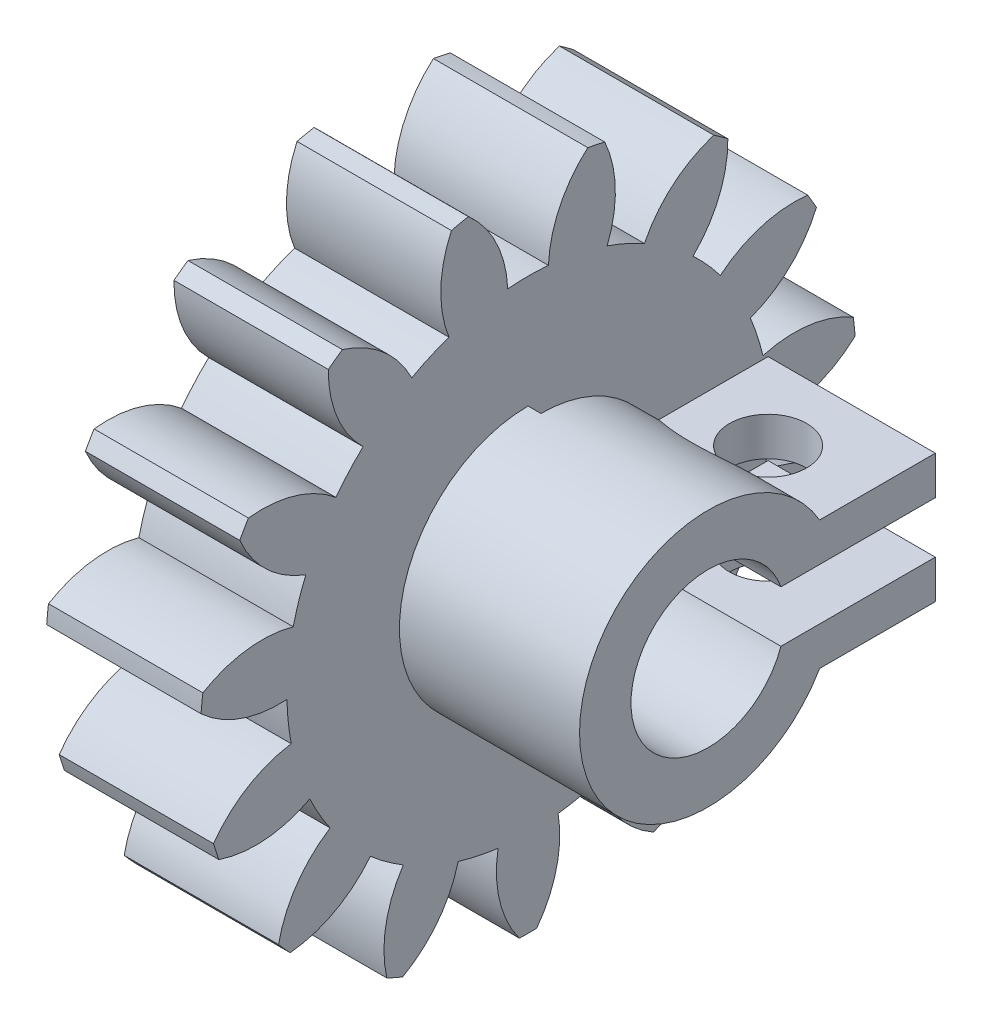
SolidWorks part; units mm, degrees
ref_plane "Plane1" through (0, 0, 0) normal (0, 0, 1) x (1, 0, 0)
ref_plane "Plane2" through (0, 0, 0) normal (0, 1, 0) x (1, 0, 0)
ref_plane "Plane3" through (0, 0, 0) normal (1, 0, 0) x (0, 0, -1)
sketch "HoldingSke" plane through (0, 0, 0) normal (0, 1, 0) x (1, 0, 0)
  line L0 (0, 0) -> (0.644, -0.1725)
  line L1 (-15, 0) -> (100, 0) construction
  line L2 (0, 0) -> (-2.1039, 2.3779)
  line L3 (0, 0) -> (-11.863, 4.5341)
  line L4 (0, 0) -> (8.3417, 2.2352)
  line L5 (0, 0) -> (-46.8476, -17.4728)
  line L6 (0, 0) -> (-4.9738, -3.3558)
  line L7 (-2.1039, 2.3779) -> (8.6586, 51.2059)
  line L8 (-76.2, 54.61) -> (-75.2, 54.61)
  line L9 (-71.009, 38.7566) -> (-53.1078, 45.2721)
  line L10 (-76.2, 71.12) -> (104.1128, 71.12)
  line L11 (0, 0) -> (-6, 0)
  line L12 (-76.2, 101.6) -> (-76.147, 101.6)
  line L13 (24.9733, 27.94) -> (52.9518, 28.4284)
  line L14 (24.9733, 27.94) -> (24.9743, 27.94)
  line L15 (24.9733, 27.94) -> (100.4006, 29.5858)
  line L16 (-63.627, -1.5) -> (-12.827, -1.5)
  circle A0 centre (0, 0) radius 3
  circle A1 centre (0, 0) radius 9.374
  circle A2 centre (0, 0) radius 37.5
  circle A3 centre (0, 0) radius 3
  dimension "Num_teeth" = 15
  dimension "Pitch_radius" = 180.3128
  dimension "Width" = 6
  dimension "Thickness" = 6
sketch "BasProSke" plane through (0, 0, 0) normal (0, 1, 0) x (1, 0, 0)
  line L0 (-10, 0) -> (60, 0) construction
  line L1 (0, 0) -> (0, 12.75)
  line L2 (0, 0) -> (6, 0)
  line L3 (6, 0) -> (6, 12.75)
  line L4 (6, 12.75) -> (0, 12.75)
  dimension "Thickness" = 6
  dimension "Diameter" = 25.5
revolve "Base-Revolve" add sketch "BasProSke" angle 360 about L0
sketch "TooCutSke" plane through (0, 0, 0) normal (1, 0, 0) x (0, 0, -1)
  line L1 (0, 0) -> (0, 107) construction
  line L2 (0, 0) -> (-1.2686, 11.1782) construction
  line L3 (0, 0) -> (-4.6563, 21.9061) construction
  line L4 (-1.2686, 11.1782) -> (-2.3281, 10.953) construction
  arc A0 (0.7915, 9.3405) -> (-0.7915, 9.3405) centre (0, 0) ccw
  arc A1 (2.3447, 12.5584) -> (-2.3447, 12.5584) centre (0, 0) ccw
  circle A2 centre (0, 0) radius 11.25 construction
  circle A3 centre (0, 0) radius 10.5715 construction
  arc A4 (-0.7915, 9.3405) -> (-2.3447, 12.5584) centre (-5.2877, 9.1541) ccw
  arc A5 (2.3447, 12.5584) -> (0.7915, 9.3405) centre (5.2877, 9.1541) ccw
extrude "ToothCut" cut sketch "TooCutSke" along normal through all
fillet "Breaks" [suppressed] radius 0.03 tangent propagation no
fillet "RootFillets" [suppressed] radius 0.376
pattern_circular "TeethCuts" count 15 every 24 about axis through (-10, 0, 0) along (1, 0, 0) of "ToothCut", "RootFillets", "Breaks"
sketch "HubNeaOneSke" plane through (0, 0, 0) normal (-1, 0, 0) x (0, 0, 1)
  circle A0 centre (0, 0) radius 9.374
  dimension "Diameter" = 18.748
extrude "HubNearOne" [suppressed] add sketch "HubNeaOneSke" along normal blind 44.0001
sketch "HubNeaBotSke" plane through (0, 0, 0) normal (-1, 0, 0) x (0, 0, 1)
  circle A0 centre (0, 0) radius 9.374
  dimension "Diameter" = 18.748
extrude "HubNearBoth" [suppressed] add sketch "HubNeaBotSke" along normal blind 22
ref_plane "FarPln" through (6, 0, 0) normal (1, 0, 0) x (0, 0, -1)
sketch "HubFarSke" plane through (6, 0, 0) normal (1, 0, 0) x (0, 0, -1)
  circle A0 centre (0, 0) radius 9.374
  dimension "Diameter" = 18.748
extrude "HubFar" [suppressed] add sketch "HubFarSke" along normal blind 22
sketch "BorSke" plane through (0, 0, 0) normal (1, 0, 0) x (0, 0, -1)
  circle A0 centre (0, 0) radius 3
  dimension "Diameter" = 6
extrude "Bore" cut sketch "BorSke" along normal mid plane 100.0001
sketch "KeySke" plane through (0, 0, 0) normal (1, 0, 0) x (0, 0, -1)
  line L0 (-1, 0) -> (-1, 4)
  line L1 (-1, 4) -> (1, 4)
  line L2 (1, 4) -> (1, 0)
  line L3 (0, 0) -> (0, 34) construction
  line L4 (-1, 0) -> (1, 0)
  dimension "Width" = 2
extrude "Keyway" [suppressed] cut sketch "KeySke" along normal mid plane 100.0001
pattern_circular "Keyway2" [suppressed] count 2 every 90 about axis through (-10, 0, 0) along (1, 0, 0) reverse direction yes
sketch "Sketch1" plane through (6, 0, 0) normal (1, 0, 0) x (0, 0, -1)
  circle A0 centre (0, 0) radius 5
  circle A1 centre (0, 0) radius 3 construction
  circle A2 centre (0, 0) radius 3
  dimension "D1" = 2
extrude "Boss-Extrude1" add sketch "Sketch1" along normal blind 7
sketch "Sketch2" plane through (13, 0, 0) normal (1, 0, 0) x (0, 0, -1)
  line L1 (1.3232, -1) -> (5.7963, -1)
  line L2 (1.3232, -1) -> (1.3232, 1)
  line L3 (1.3232, 1) -> (5.7963, 1)
  line L4 (5.7963, -1) -> (5.7963, 1)
  line L5 (1.3232, -1) -> (5.7963, 1) construction
  line L6 (1.3232, 1) -> (5.7963, -1) construction
  point P0 (3.5597, 0)
  point P5 (3.5998, 0)
  point P6 (3.5597, 0)
  point P8 (3.5597, 0)
  dimension "D1" = 2
extrude "Cut-Extrude1" cut sketch "Sketch2" against normal up to surface (7 mm away) contours L3 L4 L1 L2 up to face at (6, 0, 0)
sketch "Sketch3" plane through (0, -1, 0) normal (0, 1, 0) x (1, 0, 0)
  line L1 (6, 2.8284) -> (13, 2.8284)
  line L2 (6, 2.8284) -> (6, 8.8284)
  line L3 (6, 8.8284) -> (13, 8.8284)
  line L4 (13, 2.8284) -> (13, 8.8284)
  dimension "D1" = 6
extrude "Boss-Extrude2" add sketch "Sketch3" against normal blind 1.5
mirror "Mirror2" about plane through (0, 0, 0) normal (0, 1, 0) of "Boss-Extrude2"
sketch "Sketch4" plane through (0, -1, 0) normal (0, 1, 0) x (1, 0, 0)
  line L0 (6, 2.8284) -> (13, 8.8284) construction
  line L1 (6, 8.8284) -> (13, 2.8284) construction
  circle A0 centre (9.5, 5.8284) radius 1.5
  dimension "D1" = 3
extrude "Cut-Extrude2" cut sketch "Sketch4" against normal through all and the other way through all contours A0
sketch "Sketch5" plane through (0, 2.5, 0) normal (0, 1, 0) x (1, 0, 0)
  line L0 (6, 8.8284) -> (13, 2.8284) construction
  circle A0 centre (9.5, 5.8284) radius 3
  dimension "D1" = 6
extrude "Cut-Extrude3" cut sketch "Sketch5" along normal through all contours A0
mirror "Mirror3" about plane through (0, 0, 0) normal (0, 1, 0) of "Cut-Extrude3"
sketch "Sketch6" plane through (0, 0, 0) normal (0, 0, 1) x (1, 0, 0)
  line L0 (6, -8.278) -> (6, -5.3558) construction
  line L1 (6.5, 13.3231) -> (6, 13.3231)
  line L2 (6.5, 13.3231) -> (6.5, -14.0698)
  line L3 (6.5, -14.0698) -> (6, -14.0698)
  line L4 (6, 13.3231) -> (6, -14.0698)
  line L5 (6.5, 13.3231) -> (6, -14.0698) construction
  line L6 (6.5, -14.0698) -> (6, 13.3231) construction
  point P0 (6.25, -0.3734)
  point P7 (7.1755, 0)
  dimension "D1" = 0.5
extrude "Cut-Extrude4" cut sketch "Sketch6" against normal through all
equation "' \"Module@HoldingSke\" = 6.35"
equation "' \"Num_teeth@HoldingSke\" = 12"
equation "' \"Ap@HoldingSke\" =  20"
equation "' \"Ap@HoldingSke\" = 20"
equation "' \"Width@HoldingSke\" = 0.5 * 25.4"
equation "' \"Hub_dia@HoldingSke\"= 1 * 25.4"
equation "' \"Hub_dia@HoldingSke\" = 1 * 25.4"
equation "' \"Overall_len@HoldingSke\" = 1.0 * 25.4"
equation "' \"Bore@HoldingSke\" = 0.75 * 25.4"
equation "' \"T_dim@HoldingSke\" = 0.1 * 25.4"
equation "' \"Width@KeySke\" = 0.25 * 25.4"
equation "' \"Show_teeth@HoldingSke\" = 13"
equation "' \"Backlash@HoldingSke\" = 0.009 * 25.4"
equation "' \"Addendum_fac@HoldingSke\" = 1.0"
equation "' \"Dedendum_fac@HoldingSke\" = 1.25"
equation "' \"Dedendum_add@HoldingSke\" = 0.00005 * 25.4"
equation "' \"Clearance_fac@HoldingSke\" = 0.25"
equation "\"Pitch@HoldingSke\" = 1 / \"Module@HoldingSke\""
equation "\"Overcut_dia@TooCutSke\" = (\"Num_teeth@HoldingSke\" + 2 * \"Addendum_fac@HoldingSke\") / \"Pitch@HoldingSke\" + 0.002 * 25.4"
equation "\"Pitch_dia@TooCutSke\" = \"Num_teeth@HoldingSke\" / \"Pitch@HoldingSke\""
equation "\"Base_dia@TooCutSke\" = \"Num_teeth@HoldingSke\" / \"Pitch@HoldingSke\" * cos((\"Ap@HoldingSke\"  * 3.14159265 / 180))"
equation "\"Root_dia@TooCutSke\" = (\"Num_teeth@HoldingSke\" + 2) / \"Pitch@HoldingSke\" - 2 * (\"Addendum_fac@HoldingSke\" + \"Dedendum_fac@HoldingSke\") / \"Pitch@HoldingSke\" - \"Dedendum_add@HoldingSke\" * 2"
equation "\"Half_ang@TooCutSke\" = 180 / \"Num_teeth@HoldingSke\""
equation "\"Half_CT@TooCutSke\" = \"Num_teeth@HoldingSke\" / \"Pitch@HoldingSke\" * sin((3.14159265 / 2 / \"Num_teeth@HoldingSke\")) / 2 - 7 * \"Backlash@HoldingSke\" / 4"
equation "\"Flank_rad@TooCutSke\" = \"Num_teeth@HoldingSke\" / \"Pitch@HoldingSke\" / 5"
equation "\"Radius@RootFillets\" = \"Clearance_fac@HoldingSke\" / \"Pitch@HoldingSke\" + \"Dedendum_add@HoldingSke\""
equation "\"Break_rad@Breaks\" = 0.02 / \"Pitch@HoldingSke\""
equation "\"Thickness@HoldingSke\" = \"Width@HoldingSke\""
equation "\"OAL@HoldingSke\" = \"Thickness@HoldingSke\""
equation "\"MHD@HoldingSke\" = (\"Num_teeth@HoldingSke\" + 2) / \"Pitch@HoldingSke\" - 2 * (\"Addendum_fac@HoldingSke\" + \"Dedendum_fac@HoldingSke\")  / \"Pitch@HoldingSke\" - \"Dedendum_add@HoldingSke\" * 2"
equation "\"MBD@HoldingSke\" = (\"Num_teeth@HoldingSke\" + 2) / \"Pitch@HoldingSke\" - 2 * (\"Addendum_fac@HoldingSke\" + \"Dedendum_fac@HoldingSke\")  / \"Pitch@HoldingSke\" - \"Dedendum_add@HoldingSke\" * 2 - 0.002 * 25.4"
equation "\"MHD@HoldingSke\" = ((sgn( \"MHD@HoldingSke\" - \"Hub_dia@HoldingSke\" )-1)*( \"MHD@HoldingSke\" - \"Hub_dia@HoldingSke\" ))/-2+ \"Hub_dia@HoldingSke\""
equation "\"MBD@HoldingSke\" = ((sgn( \"MBD@HoldingSke\" - \"Bore@HoldingSke\" )-1)*( \"MBD@HoldingSke\" - \"Bore@HoldingSke\" ))/-2+ \"Bore@HoldingSke\""
equation "\"OAL@HoldingSke\" = ((sgn( \"OAL@HoldingSke\" - \"Overall_len@HoldingSke\" )+1)*( \"OAL@HoldingSke\" - \"Overall_len@HoldingSke\" ))/2 + \"Overall_len@HoldingSke\" + 0.000002 * 25.4"
equation "\"Num_teeth@TeethCuts\" = int( \"Show_teeth@HoldingSke\" ) + 1"
equation "\"Num_teeth@TeethCuts\" = ((sgn( \"Num_teeth@TeethCuts\" - \"Num_teeth@HoldingSke\" )-1)*( \"Num_teeth@TeethCuts\" - \"Num_teeth@HoldingSke\" ))/-2+ \"Num_teeth@HoldingSke\""
equation "\"Num_teeth@TeethCuts\" = ((sgn( \"Num_teeth@TeethCuts\" - 2.0)+1)*( \"Num_teeth@TeethCuts\" - 2.0))/2 +2.0"
equation "\"Angle@TeethCuts\" = 360.0 / \"Num_teeth@HoldingSke\""
equation "\"Diameter@BasProSke\" = (\"Num_teeth@HoldingSke\" + 2 * \"Addendum_fac@HoldingSke\") / \"Pitch@HoldingSke\""
equation "\"Thickness@BasProSke\"  = \"Thickness@HoldingSke\""
equation "' \"Fillet_rad@BasProSke\" =  \"Thickness@HoldingSke\" * 0.05"
equation "' \"Fillet_rad@BasProSke\" = \"Thickness@HoldingSke\" * 0.05"
equation "\"MHD@HoldingSke\" = ((sgn( \"MHD@HoldingSke\" - \"Root_dia@TooCutSke\" )-1)*( \"MHD@HoldingSke\" - \"Root_dia@TooCutSke\" ))/-2+ \"Root_dia@TooCutSke\""
equation "\"Diameter@HubNeaOneSke\" = \"MHD@HoldingSke\""
equation "\"Length@HubNearOne\" = \"OAL@HoldingSke\" - \"Thickness@BasProSke\""
equation "\"Diameter@HubNeaBotSke\" = \"MHD@HoldingSke\""
equation "\"Length@HubNearBoth\" = ( \"OAL@HoldingSke\" - \"Thickness@BasProSke\" ) / 2.0"
equation "\"Thickness@FarPln\" = \"Thickness@BasProSke\""
equation "\"Diameter@HubFarSke\" = \"MHD@HoldingSke\""
equation "\"Length@HubFar\" = ( \"OAL@HoldingSke\" - \"Thickness@BasProSke\" ) / 2.0"
equation "\"Diameter@BorSke\" = \"MBD@HoldingSke\""
equation "\"D1@Bore\" = \"OAL@HoldingSke\" * 2.0"
equation "\"D1@Keyway\" = \"OAL@HoldingSke\" * 2.0"
equation "\"Offset@KeySke\" = \"T_dim@HoldingSke\" + \"MBD@HoldingSke\" / 2.0"
